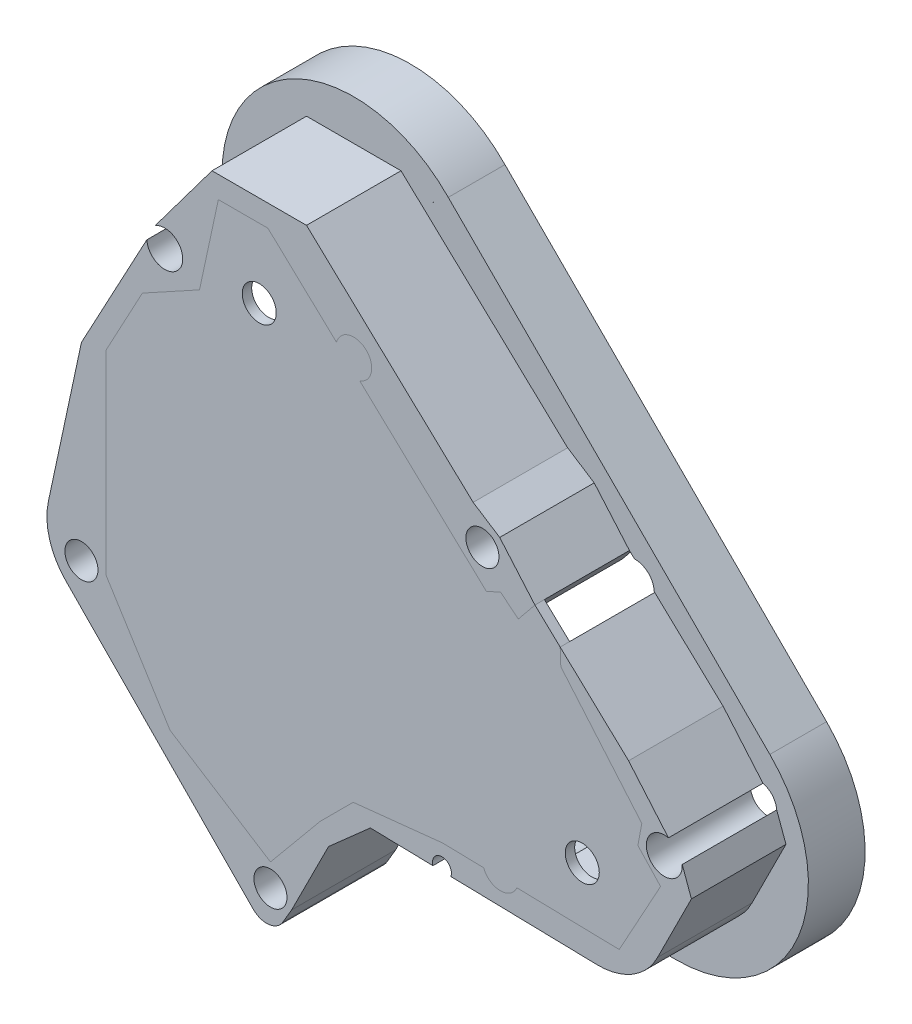
SolidWorks part; units mm, degrees
ref_plane "Front Plane" through (0, 0, 0) normal (0, 0, 1) x (1, 0, 0)
ref_plane "Top Plane" through (0, 0, 0) normal (0, 1, 0) x (1, 0, 0)
ref_plane "Right Plane" through (0, 0, 0) normal (1, 0, 0) x (0, 0, -1)
sketch "Sketch1" plane through (0, 0, 0) normal (0, 0, 1) x (1, 0, 0)
  line L0 (-49.657, 3.175) -> (-52.07, 3.175)
  line L1 (3.175, -49.657) -> (3.175, -52.07)
  line L2 (-51.802, -3.6533) -> (-1.4757, -54.8508)
  line L3 (6.5297, -53.8584) -> (8.8674, -49.8701)
  line L4 (8.8674, -49.8701) -> (18.7949, -30.1557)
  line L5 (18.7949, -30.1557) -> (30.0155, -20.2243)
  line L6 (-56.5073, 12.5372) -> (-47.625, 53.975)
  line L7 (74.2512, 53.7721) -> (75.8197, 47.3959)
  line L8 (-47.625, 53.975) -> (-30.0542, 86.6324)
  line L9 (-12.54, 111.4557) -> (12.86, 111.4557)
  line L10 (12.86, 111.4557) -> (57.648, 69.3725)
  line L11 (61.5659, 61.5659) -> (60.1381, 60.1381)
  line L12 (80.4118, 49.5683) -> (108.3948, 21.5853)
  line L13 (-27.8115, 91.0533) -> (-12.54, 111.4557)
  line L14 (99.4208, 30.1224) -> (110.1323, 17.5308)
  line L15 (116.3112, 6.41) -> (107.2003, -11.7745)
  line L16 (90.9065, -21.5855) -> (30.0155, -20.2243)
  line L17 (3.175, -41.5588) -> (-23.8102, -24.4098)
  line L18 (59.153, 70.8271) -> (108.3948, 21.5853) construction
  line L19 (81.0371, 47.3959) -> (80.898, 47.5266)
  line L20 (113.8293, 13.1848) -> (116.3112, 6.41)
  line L21 (-41.0684, 3.175) -> (-41.0684, 55.3774)
  line L22 (-41.0684, 55.3774) -> (-31.252, 73.6224)
  line L23 (-31.252, 73.6224) -> (-15.8919, 82.061)
  line L24 (-15.8919, 82.061) -> (-10.836, 105.6006)
  line L25 (69.7886, 48.2829) -> (74.2512, 53.7721)
  line L26 (-10.836, 105.6006) -> (2.4862, 105.6006)
  line L27 (81.2029, 42.899) -> (81.0371, 47.3959)
  line L28 (2.4862, 105.6006) -> (20.9163, 88.2835)
  line L29 (61.2432, 50.3919) -> (64.9724, 52.1984)
  line L30 (64.9724, 52.1984) -> (69.7886, 48.2829)
  line L31 (57.648, 69.3725) -> (64.7779, 64.7779)
  line L33 (64.7779, 64.7779) -> (74.2512, 53.7721)
  line L34 (81.2029, 42.899) -> (102.9786, 17.3008)
  line L36 (108.0179, 5.158) -> (96.902, -15.0756)
  line L37 (81.0371, 47.3959) -> (99.4208, 30.1224)
  line L38 (96.902, -15.0756) -> (69.3997, -14.4607)
  line L39 (49.3931, -14.0135) -> (25.4, -16.5608)
  line L40 (25.4, -16.5608) -> (16.5608, -25.4)
  line L41 (16.5608, -25.4) -> (3.175, -41.5588)
  line L42 (-23.8102, -24.4098) -> (-41.0684, 3.175)
  line L43 (27.1603, 82.4165) -> (61.2432, 50.3919)
  line L44 (60.4637, -14.261) -> (49.3931, -14.0135)
  line L45 (108.0179, 5.158) -> (101.916, 11.6393)
  line L46 (101.916, 11.6393) -> (102.9786, 17.3008)
  line L47 (57.15, -30.14) -> (57.15, -20.8309)
  line L48 (27.7989, 74.5425) -> (6.5297, 27.2377)
  line L49 (81.0371, 47.3959) -> (74.2512, 53.7721)
  line L50 (21.2342, 108.7459) -> (59.153, 70.8271)
  line L51 (59.153, 70.8271) -> (77.9921, 51.988)
  line L52 (86.9695, -30.14) -> (57.15, -30.14)
  line L53 (69.7886, 48.2829) -> (75.8197, 47.3959)
  line L54 (49.3931, -14.0135) -> (49.2625, -19.8555)
  line L55 (-35.22, 86.433) -> (-35.22, 77.0312)
  line L56 (24.8264, 112.338) -> (62.7451, 74.4192)
  line L57 (62.7451, 74.4192) -> (111.9869, 25.1774)
  line L58 (86.9695, -35.22) -> (57.15, -35.22)
  line L59 (-35.22, 86.433) -> (-35.22, 74.2333) construction
  line L60 (52.07, -35.22) -> (52.07, -29.84) construction
  line L61 (57.15, -30.14) -> (57.15, -35.22)
  line L62 (86.9695, -35.22) -> (52.07, -35.22) construction
  line L63 (-30.14, 86.473) -> (-30.14, 74.2333) construction
  line L64 (57.15, -30.14) -> (57.15, -29.84) construction
  line L65 (81.0371, 47.3959) -> (75.8197, 47.3959)
  circle A0 centre (-47.625, 3.175) radius 2.032
  circle A1 centre (3.175, -47.625) radius 2.032
  circle A2 centre (60.1381, 60.1381) radius 2.0193
  arc A3 (80.4118, 49.5683) -> (77.9921, 51.988) centre (75.8197, 47.3959) ccw
  arc A4 (-30.0542, 86.6324) -> (-27.8115, 91.0533) centre (-25.24, 86.9695) ccw
  circle A5 centre (-47.625, 3.175) radius 4.445
  circle A6 centre (60.1381, 60.1381) radius 4.445
  arc A7 (80.898, 47.5266) -> (75.6342, 52.4725) centre (75.8197, 47.3959) ccw
  circle A9 centre (3.175, -47.625) radius 4.445
  arc A10 (21.9364, 108.0437) -> (-30.14, 86.473) centre (0.16, 86.9695) ccw
  circle A11 centre (86.9695, 0.16) radius 4.572
  circle A12 centre (0.16, 86.9695) radius 4.572
  arc A13 (51.6552, -20.708) -> (46.8342, -20.6003) centre (49.2625, -19.8555) ccw
  arc A14 (27.1603, 82.4165) -> (20.9163, 88.2835) centre (25.56, 86.9695) ccw
  arc A15 (60.4637, -14.261) -> (69.3997, -14.4607) centre (64.9724, -12.54) ccw
  arc A16 (86.9695, -30.14) -> (108.3948, 21.5853) centre (86.9695, 0.16) ccw
  arc A17 (110.1323, 17.5308) -> (113.8293, 13.1848) centre (109.0159, 12.8357) ccw
  arc A18 (-1.4757, -54.8508) -> (6.5297, -53.8584) centre (2.1471, -51.2896) ccw
  arc A19 (-51.802, -3.6533) -> (-56.5073, 12.5372) centre (-39.1222, 8.8107) cw
  arc A20 (90.9065, -21.5855) -> (107.2003, -11.7745) centre (91.3039, -3.81) ccw
  arc A21 (25.5869, 111.5765) -> (-35.22, 86.433) centre (0.16, 86.9695) ccw
  arc A22 (86.9695, -35.22) -> (111.9869, 25.1774) centre (86.9695, 0.16) ccw
  circle A23 centre (109.0159, 12.8357) radius 4.826
  circle A24 centre (-25.24, 86.9695) radius 4.826
  dimension "D1" = 4.064
  dimension "D2" = 4.064
  dimension "D4" = 9.652
  dimension "D5" = 8.89
  dimension "D3" = 5.08
  dimension "D6" = 17.78
  dimension "D7" = 17.78
  dimension "D8" = 8.89
  dimension "D9" = 8.89
  dimension "D10" = 9.144
  dimension "D13" = 9.144
  dimension "D21" = 10.16
  dimension "D23" = 5.08
  dimension "D11" = 9.9326
  dimension "D12" = 15.0098
  dimension "D14" = 2.3262
  dimension "D15" = 18.6311
  dimension "D16" = 0.1811
  dimension "D17" = 6.096
  dimension "D20" = 6.5662
  dimension "D22" = 5.842
  dimension "D18" = 5.08
  dimension "D19" = 5.08
extrude "Boss-Extrude1" add sketch "Sketch1" along normal blind 27.94 contours L16 A20 L15 L20 A17 L14 L37 L27 L34 L46 L45 L36 L38 A15 L44 L54 A13 | A19 L2 A18 L3 L4 L5 L16 A13 L54 L39 L40 L41 L17 L42 L21 L22 L23 L24 L26 L28 A14 L43 L29 L30 L25 L33 L31 L10 L9 L13 A4 L8 L6 A9 A6 A5 | L9 L10 L31 L33 L25 L30 L29 L43 A14 L28 L26 L24 L23 L22 L21 L42 L17 L41 L40 L39 L44 A15 L38 L36 L45 L46 L34 L27 L37 L14 A17 L20 L15 A20 L16 L5 L4 L3 A18 L2 A19 L6 L8 A4 L13 | A6 | A9 | A5 region at (-54.1505, 4.4432, 0) region at (52.1464, -17.8694, 0)
extrude "Boss-Extrude2" add sketch "Sketch1<4>" along normal blind 5.08 contours A6 A2 | A9 A1 | A5 A0 region at (-47.625, 7.4943, 0) region at (0.1208, -44.5708, 0) region at (55.8188, 60.1381, 0)
sketch "Sketch1<4>" plane through (0, 0, 0) normal (0, 0, 1) x (1, 0, 0) same geometry as "Sketch1"
extrude "Boss-Extrude3" add sketch "Sketch1<5>" along normal blind 2.54 contours A24 L13 L9 L10 L31 L33 L49 L37 L14 A23 L20 L15 A20 L16 L47 L52 A16 L51 L50 A10 L8 region at (-11.3916, 113.6141, 0)
sketch "Sketch1<5>" plane through (0, 0, 0) normal (0, 0, 1) x (1, 0, 0) same geometry as "Sketch1"
extrude "Boss-Extrude4" add sketch "Sketch1<6>" along normal blind 2.54 and the other way blind 12.7 contours L58 A22 L57 L56 A21 L55 L8 A10 L50 L51 A16 L52 L61 region at (-32.9916, 81.7321, 0)
sketch "Sketch1<6>" plane through (0, 0, 0) normal (0, 0, 1) x (1, 0, 0) same geometry as "Sketch1"
sketch "Sketch2" plane through (0, 0, 27.94) normal (0, 0, 1) x (1, 0, 0)
  line L0 (-10.836, 105.6006) -> (-15.8919, 82.061)
  line L1 (-15.8919, 82.061) -> (-31.252, 73.6224)
  line L2 (-31.252, 73.6224) -> (-41.0684, 55.3774)
  line L3 (-41.0684, 55.3774) -> (-41.0684, 3.175)
  line L4 (-41.0684, 3.175) -> (-23.8102, -24.4098)
  line L5 (-23.8102, -24.4098) -> (3.175, -41.5588)
  line L6 (3.175, -41.5588) -> (16.5608, -25.4)
  line L7 (16.5608, -25.4) -> (25.4, -16.5608)
  line L8 (25.4, -16.5608) -> (49.3931, -14.0135)
  line L9 (49.3931, -14.0135) -> (60.4637, -14.261)
  line L11 (69.3997, -14.4607) -> (96.902, -15.0756)
  line L12 (96.902, -15.0756) -> (108.0179, 5.158)
  line L13 (108.0179, 5.158) -> (101.916, 11.6393)
  line L14 (101.916, 11.6393) -> (102.9786, 17.3008)
  line L15 (102.9786, 17.3008) -> (81.2029, 42.899)
  line L16 (81.2029, 42.899) -> (81.0371, 47.3959)
  line L17 (81.0371, 47.3959) -> (74.2512, 53.7721)
  line L18 (74.2512, 53.7721) -> (69.7886, 48.2829)
  line L19 (69.7886, 48.2829) -> (64.9724, 52.1984)
  line L20 (64.9724, 52.1984) -> (61.2432, 50.3919)
  line L21 (61.2432, 50.3919) -> (27.1603, 82.4165)
  line L22 (20.9163, 88.2835) -> (2.4862, 105.6006)
  line L23 (2.4862, 105.6006) -> (-10.836, 105.6006)
  arc A0 (60.4637, -14.261) -> (69.3997, -14.4607) centre (64.9724, -12.54) ccw
  arc A1 (27.1603, 82.4165) -> (20.9163, 88.2835) centre (25.56, 86.9695) ccw
extrude "Boss-Extrude5" add sketch "Sketch2" against normal blind 2.54 separate body
extrude "Cut-Extrude2" cut sketch "Sketch1<10>" along normal through all contours A13 L16 region at (47.2858, -18.3597, 0)
sketch "Sketch1<10>" plane through (0, 0, 0) normal (0, 0, 1) x (1, 0, 0) same geometry as "Sketch1"
extrude "Boss-Extrude7" add sketch "Sketch1<11>" along normal blind 2.54 contours A23 L20 L15 A20 L16 L47 L52 A16 L12 A7 L19 L37 L14 region at (74.0059, -22.2063, 0)
sketch "Sketch1<11>" plane through (0, 0, 0) normal (0, 0, 1) x (1, 0, 0) same geometry as "Sketch1"
extrude "Cut-Extrude1" cut sketch "Sketch1<7>" along normal through all contours A12 | A11 region at (86.9695, 0.16, 0) region at (0.16, 86.9695, 0)
sketch "Sketch1<7>" plane through (0, 0, 0) normal (0, 0, 1) x (1, 0, 0) same geometry as "Sketch1"
extrude "Boss-Extrude6" add sketch "Sketch1<9>" along normal blind 2.54 contours A23 L20 L15 A20 L16 L47 L52 A16 L12 A7 L19 L37 L14 region at (74.0059, -22.2063, 0)
sketch "Sketch1<9>" plane through (0, 0, 0) normal (0, 0, 1) x (1, 0, 0) same geometry as "Sketch1"
